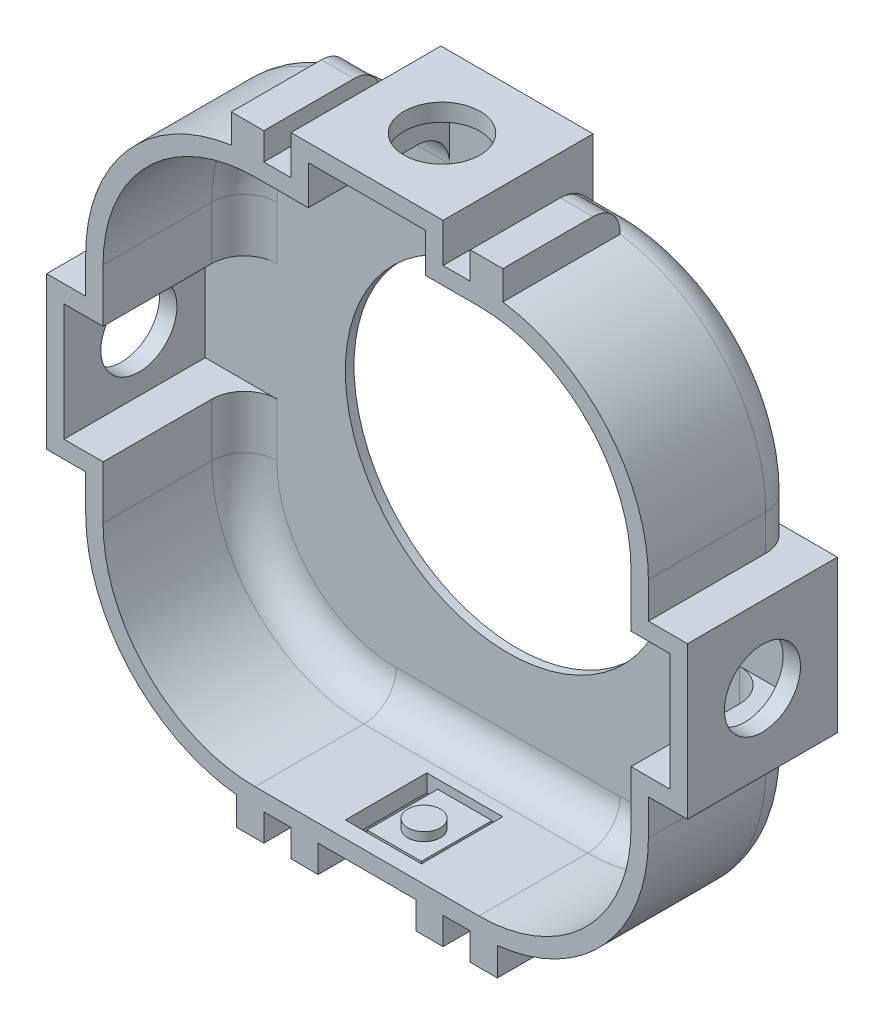
SolidWorks part; units mm, degrees
ref_plane "Спереди" through (0, 0, 0) normal (0, 0, 1) x (1, 0, 0)
ref_plane "Сверху" through (0, 0, 0) normal (0, 1, 0) x (1, 0, 0)
ref_plane "Справа" through (0, 0, 0) normal (1, 0, 0) x (0, 0, -1)
sketch "Эскиз-База" plane through (0, 0, 0) normal (0, 0, 1) x (1, 0, 0)
  line L0 (29.5, 0) -> (-29.5, 0) construction
  line L1 (-25.9, 25.9) -> (25.9, 25.9) construction
  line L2 (-25.9, 25.9) -> (-25.9, -25.9) construction
  line L3 (-25.9, -25.9) -> (25.9, -25.9) construction
  line L4 (25.9, 25.9) -> (25.9, -25.9) construction
  line L5 (-25.9, 25.9) -> (25.9, -25.9) construction
  line L6 (-25.9, -25.9) -> (25.9, 25.9) construction
  line L7 (0, -25.9) -> (0, 29.5) construction
  line L8 (-25.9, 7) -> (-29.5, 7)
  line L9 (-29.5, 7) -> (-29.5, -7)
  line L10 (-29.5, -7) -> (-25.9, -7)
  line L11 (25.9, 7) -> (29.5, 7)
  line L12 (29.5, 7) -> (29.5, -7)
  line L13 (29.5, -7) -> (25.9, -7)
  line L14 (-25.9, 10.3) -> (-25.9, 7)
  line L15 (-25.9, -10.3) -> (-25.9, -7)
  line L16 (-10.3, -25.9) -> (10.3, -25.9)
  line L17 (25.9, -10.3) -> (25.9, -7)
  line L18 (25.9, 7) -> (25.9, 10.3)
  line L19 (-7, 25.9) -> (-7, 29.5)
  line L20 (-7, 29.5) -> (7, 29.5)
  line L21 (7, 29.5) -> (7, 25.9)
  line L25 (-10.3, 25.9) -> (-7, 25.9)
  line L26 (7, 25.9) -> (10.3, 25.9)
  arc A0 (-25.9, 10.3) -> (-10.3, 25.9) centre (-10.3, 10.3) cw
  arc A1 (25.9, 10.3) -> (10.3, 25.9) centre (10.3, 10.3) ccw
  arc A2 (25.9, -10.3) -> (10.3, -25.9) centre (10.3, -10.3) cw
  arc A3 (-25.9, -10.3) -> (-10.3, -25.9) centre (-10.3, -10.3) ccw
  circle A4 centre (0, 0) radius 15
  point P0 (0, 0)
  point P17 (-29.5, 0)
  point P24 (29.5, 0)
  point P36 (0, 29.5)
  dimension "D2" = 15.6
  dimension "D3" = 15.6
  dimension "D5" = 59
  dimension "D6" = 14
  dimension "D8" = 30
  dimension "D1" = 51.8
  dimension "D4" = 14
  dimension "D7" = 29.5
extrude "Вытянуть-Стенки" add sketch "Эскиз-База" along normal blind 13 from surface thin contours A0 L25 L19 L20 L21 L26 A1 L18 L11 L12 L13 L17 A2 L16 A3 L15 L10 L9 L8 L14 starting at plane "Спереди" thin type one direction reverse wall 1.6
extrude "Бобышка-Дно" add sketch "Эскиз-База<8>" against normal blind 0.8
sketch "Эскиз-База<8>" plane through (0, 0, 0) normal (0, 0, 1) x (1, 0, 0) same geometry as "Эскиз-База"
sketch "Эскиз-Левое отверстие" plane through (-29.5, 0, 0) normal (-1, 0, 0) x (0, 0, 1)
  line L0 (-0.8, 7) -> (13, -7) construction
  line L1 (-0.8, -7) -> (13, 7) construction
  circle A0 centre (6.1, 0) radius 3.5
  dimension "D1" = 7
extrude "Вырез-Отверстия слева справа" cut sketch "Эскиз-Левое отверстие" against normal up to surface (59 mm away)
sketch "Эскиз-Отверстие сверху" plane through (0, 29.5, 0) normal (0, 1, 0) x (1, 0, 0)
  line L0 (-7, 0.8) -> (7, -13) construction
  line L1 (-7, -13) -> (7, 0.8) construction
  circle A0 centre (0, -6.1) radius 3.5
  dimension "D1" = 7
extrude "Вырез-Верхнее отверстие" cut sketch "Эскиз-Отверстие сверху" against normal up to next
sketch "Эскиз-Кнопка записи" plane through (0, -25.9, 0) normal (0, -1, 0) x (1, 0, 0)
  line L0 (-10.3, 7.75) -> (10.3, 7.75) construction
  line L1 (-10.3, 13) -> (-10.3, -0.8) construction
  line L2 (10.3, 13) -> (10.3, -0.8) construction
  line L3 (50, 0) -> (-50, 0) construction
  line L4 (0, 13) -> (0, -0.8) construction
  line L5 (-10.3, 13) -> (10.3, 13) construction
  line L6 (-10.3, -0.8) -> (10.3, -0.8) construction
  line L7 (-2.5, 4) -> (-2.5, 10.5)
  line L8 (-2.5, 10.5) -> (2.5, 10.5)
  line L9 (3.5, 4) -> (2.5, 4)
  line L10 (3.5, 11.5) -> (-3.5, 11.5)
  line L11 (-3.5, 11.5) -> (-3.5, 4)
  line L12 (-3.5, 4) -> (-2.5, 4)
  line L13 (2.5, 4) -> (2.5, 10.5)
  line L14 (3.5, 11.5) -> (3.5, 4)
  line L15 (-2.5, 4) -> (2.5, 4)
  line L16 (-2.5, 4) -> (-2.5, 2.25)
  line L17 (-2.5, 2.25) -> (2.5, 2.25)
  line L18 (2.5, 2.25) -> (2.5, 4)
  circle A0 centre (0, 7.75) radius 1.5
  point P25 (0, 10.5)
  point P26 (0, 11.5)
  dimension "D2" = 3
  dimension "D1" = 7.75
  dimension "D3" = 1
  dimension "D4" = 1
  dimension "D5" = 4
  dimension "D6" = 11.5
  dimension "D7" = 3.5
  dimension "D8" = 1.75
extrude "Вырез-Рамка кнопки" cut sketch "Эскиз-Кнопка записи" against normal up to next contours L14 L10 L11 L12 L7 L8 L13 L9 region at (-3, -25.9, 4.1026)
extrude "Вырез-Утоньшение кнопки" cut sketch "Эскиз-Кнопка записи<3>" against normal up to next from offset 0.8 contours L7 L15 L13 L8 A0 region at (-2.418, -25.9, 7.25) offset against normal yes
sketch "Эскиз-Кнопка записи<3>" plane through (0, -25.9, 0) normal (0, -1, 0) x (1, 0, 0) same geometry as "Эскиз-Кнопка записи"
fillet "Скругление-Внутреннее" radius 3 11 edges at (-24.3, -7.85, 0) (24.3, -7.85, 0) (20.1995, -20.1995, 0) (0, -24.3, 0) (24.3, 7.85, 0) (7.85, 24.3, 0) (-7.85, 24.3, 0) (-24.3, 7.85, 0) (-20.1995, -20.1995, 0) (20.1995, 20.1995, 0) (-20.1995, 20.1995, 0)
fillet "Скругление-Наружное" radius 3 11 edges at (-25.9, 8.65, -0.8) (-25.9, -8.65, -0.8) (-21.3309, -21.3309, -0.8) (0, -25.9, -0.8) (21.3309, -21.3309, -0.8) (25.9, -8.65, -0.8) (25.9, 8.65, -0.8) (21.3309, 21.3309, -0.8) (8.65, 25.9, -0.8) (-8.65, 25.9, -0.8) (-21.3309, 21.3309, -0.8)
sketch "Эскиз-Фиксатор резинки" plane through (0, 0, 0) normal (0, 0, 1) x (1, 0, 0)
  line L0 (-9.5, 25.9) -> (-9.5, 28.4)
  line L1 (-7, 25.9) -> (-10.3, 25.9) construction
  line L2 (-9.5, 28.4) -> (-12.5, 28.4)
  line L3 (-12.5, 28.4) -> (-12.5, 25.4)
  line L4 (12, -25.4) -> (9.5, -25.9)
  line L5 (-7, 29.5) -> (-7, 25.9) construction
  line L6 (0, 29.5) -> (0, -25.9) construction
  line L7 (7, 29.5) -> (-7, 29.5) construction
  line L8 (10.3, -25.9) -> (-10.3, -25.9) construction
  line L9 (9.5, 25.9) -> (9.5, 28.4)
  line L10 (9.5, 28.4) -> (12.5, 28.4)
  line L11 (12.5, 25.4) -> (9.5, 25.9)
  line L12 (-9.5, -25.9) -> (-9.5, -28.4)
  line L13 (-9.5, -28.4) -> (-12, -28.4)
  line L14 (-12, -28.4) -> (-12, -25.4)
  line L15 (9.5, -28.4) -> (12, -28.4)
  line L16 (9.5, -25.9) -> (9.5, -28.4)
  line L17 (-12, -25.4) -> (-9.5, -25.9)
  line L18 (12, -28.4) -> (12, -25.4)
  line L19 (-12.5, 25.4) -> (-9.5, 25.9)
  line L20 (12.5, 28.4) -> (12.5, 25.4)
  line L21 (-7, -25.9) -> (-7, -28.4)
  line L22 (-7, -28.4) -> (-4.5, -28.4)
  line L23 (-4.5, -28.4) -> (-4.5, -25.9)
  line L24 (-7, -25.9) -> (-4.5, -25.9)
  line L25 (4.5, -28.4) -> (4.5, -25.9)
  line L26 (7, -28.4) -> (4.5, -28.4)
  line L27 (7, -25.9) -> (7, -28.4)
  line L28 (7, -25.9) -> (4.5, -25.9)
  dimension "D1" = 2.5
  dimension "D2" = 3
  dimension "D3" = 2.5
  dimension "D4" = 9.5
  dimension "D5" = 2.5
  dimension "D6" = 3
  dimension "D7" = 2.5
  dimension "D8" = 3
  dimension "D9" = 2.5
  dimension "D10" = 2.5
extrude "Бобышка-Фиксатор резинки" add sketch "Эскиз-Фиксатор резинки" along normal up to surface (13 mm away) from offset 2.2 up to face at (0, 5.54, 13)
extrude "Бобышка-Утолщение кнопки" add sketch "Эскиз-Кнопка записи<5>" along normal blind 2.5 contours L17 L18 L15 L16 | L7 L15 L13 L8 A0 | A0 region at (-2.418, -25.9, 7.25) region at (0, -25.9, 3.125) region at (0, -25.9, 7.75)
sketch "Эскиз-Кнопка записи<5>" plane through (0, -25.9, 0) normal (0, -1, 0) x (1, 0, 0) same geometry as "Эскиз-Кнопка записи"
fillet "Скругление1" radius 2.5 7 edges at (10.75, -28.4, 2.2) (5.75, -28.4, 2.2) (-10.75, -28.4, 2.2) (-5.75, -28.4, 2.2) (0, -28.4, 2.25) (11, 28.4, 2.2) (-11, 28.4, 2.2)
